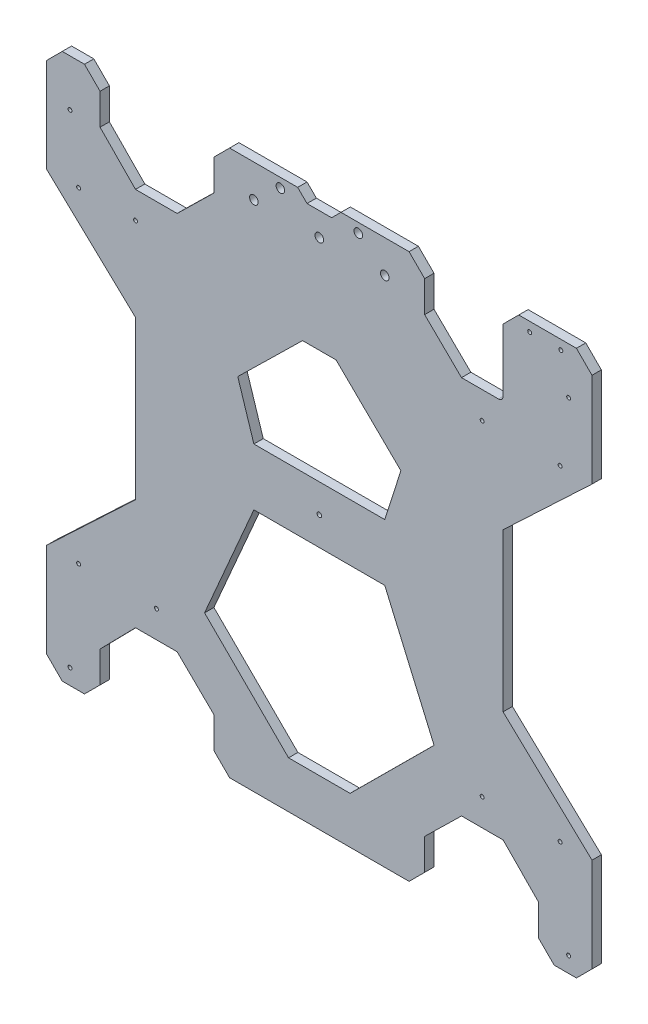
SolidWorks part; units mm, degrees
material "6063-T5"
ref_plane "Piano frontale" through (0, 0, 0) normal (0, 0, 1) x (1, 0, 0)
ref_plane "Piano superiore" through (0, 0, 0) normal (0, 1, 0) x (1, 0, 0)
ref_plane "Piano destro" through (0, 0, 0) normal (1, 0, 0) x (0, 0, -1)
sketch "Schizzo13" plane through (0, 0, 0) normal (0, 0, 1) x (1, 0, 0)
  line L0 (175, 350) -> (175, 0) construction
  line L1 (10, 0) -> (24.282, 0)
  line L2 (0, 279.5) -> (57.0808, 225.6111)
  line L3 (217, 193.2869) -> (227.343, 225.6111)
  line L4 (133, 193.2869) -> (217, 193.2869)
  line L5 (350, 175) -> (0, 175) construction
  line L6 (-60.1887, 10) -> (461.2643, 10) construction
  line L7 (279.5, 279.5) -> (279.5, 175) construction
  line L8 (-12.961, 344) -> (386.8832, 344) construction
  line L9 (-12.961, 329) -> (386.8832, 329) construction
  line L10 (161.1089, 350) -> (167.1089, 344)
  line L11 (279.5, 70.5) -> (175, 70.5) construction
  line L12 (70.5, 70.5) -> (175, 70.5) construction
  line L13 (167.1089, 344) -> (182.8911, 344)
  line L14 (57.0808, 279.5) -> (57.0808, 175) construction
  line L15 (57.0808, 279.5) -> (175, 279.5) construction
  line L16 (175, 279.5) -> (329.5, 279.5) construction
  line L17 (329.5, 70.5) -> (329.5, 279.5) construction
  line L18 (20.5, 70.5) -> (329.5, 70.5) construction
  line L19 (20.5, 70.5) -> (20.5, 279.5) construction
  line L20 (175, 279.5) -> (20.5, 279.5) construction
  line L21 (15, -40.9714) -> (15, 408.5301) construction
  line L22 (335, -40.9714) -> (335, 408.5301) construction
  line L23 (-12.961, 320) -> (386.8832, 320) construction
  line L24 (10, 0) -> (0, 10)
  line L25 (340, 0) -> (350, 10)
  line L26 (107.4046, 340) -> (107.4046, 320)
  line L27 (107.4046, 320) -> (83.7454, 296.8073)
  line L28 (57.0808, 279.5) -> (20.5, 279.5) construction
  line L29 (57.0174, 296.8073) -> (34.282, 320)
  line L30 (83.7454, 296.8073) -> (57.0174, 296.8073)
  line L31 (34.282, 320) -> (34.282, 340)
  line L32 (24.282, 350) -> (10, 350)
  line L33 (133, 193.2869) -> (122.657, 225.6111)
  line L34 (57.0808, 279.5) -> (57.0808, 350) construction
  line L35 (164.2491, 266.3832) -> (185.7509, 266.3832)
  line L36 (122.657, 225.6111) -> (164.2491, 266.3832)
  line L37 (57.0808, 225.6111) -> (57.0808, 175)
  line L38 (227.343, 225.6111) -> (185.7509, 266.3832)
  line L39 (292.9192, 225.6111) -> (292.9192, 124.3889)
  line L40 (350, 279.5) -> (292.9192, 225.6111)
  line L41 (188.8911, 350) -> (182.8911, 344)
  line L42 (117.4046, 350) -> (161.1089, 350)
  line L44 (292.9826, 299.8073) -> (292.9826, 340)
  line L46 (117.4046, 0) -> (232.5954, 0)
  line L47 (266.2546, 296.8073) -> (289.9826, 296.8073)
  line L48 (242.5954, 320) -> (266.2546, 296.8073)
  line L49 (242.5954, 340) -> (242.5954, 320)
  line L50 (350, 70.5) -> (292.9192, 124.3889)
  line L53 (350, 10) -> (350, 70.5)
  line L55 (315.718, 30) -> (315.718, 10)
  line L56 (292.9826, 53.1927) -> (315.718, 30)
  line L57 (266.2546, 53.1927) -> (292.9826, 53.1927)
  line L58 (242.5954, 30) -> (266.2546, 53.1927)
  line L59 (242.5954, 10) -> (242.5954, 30)
  line L60 (107.4046, 10) -> (107.4046, 30)
  line L61 (107.4046, 30) -> (83.7454, 53.1927)
  line L62 (83.7454, 53.1927) -> (57.0174, 53.1927)
  line L63 (57.0174, 53.1927) -> (34.282, 30)
  line L64 (34.282, 30) -> (34.282, 10)
  line L66 (0, 10) -> (0, 70.5)
  line L69 (0, 70.5) -> (57.0808, 124.3889)
  line L70 (57.0808, 124.3889) -> (57.0808, 175)
  line L71 (0, 279.5) -> (0, 340)
  line L72 (188.8911, 350) -> (232.5954, 350)
  line L73 (302.9826, 350) -> (340, 350)
  line L74 (350, 279.5) -> (350, 340)
  line L75 (325.718, 0) -> (340, 0)
  line L76 (24.282, 0) -> (34.282, 10)
  line L77 (117.4046, 0) -> (107.4046, 10)
  line L78 (232.5954, 0) -> (242.5954, 10)
  line L79 (315.718, 10) -> (325.718, 0)
  line L80 (10, 350) -> (0, 340)
  line L81 (24.282, 350) -> (34.282, 340)
  line L82 (107.4046, 340) -> (117.4046, 350)
  line L83 (232.5954, 350) -> (242.5954, 340)
  line L84 (292.9826, 340) -> (302.9826, 350)
  line L85 (340, 350) -> (350, 340)
  line L86 (133, 156.7131) -> (101.3482, 83.6168)
  line L87 (101.3482, 83.6168) -> (155.2542, 30)
  line L88 (155.2542, 30) -> (194.7458, 30)
  line L89 (133, 156.7131) -> (217, 156.7131)
  line L90 (248.6518, 83.6168) -> (194.7458, 30)
  line L91 (217, 156.7131) -> (248.6518, 83.6168)
  circle A0 centre (15, 320) radius 1.25
  circle A1 centre (20.5, 279.5) radius 1.25
  circle A2 centre (57.0808, 279.5) radius 1.25
  circle A3 centre (175, 175) radius 1.5
  arc A4 (289.9826, 296.8073) -> (292.9826, 299.8073) centre (289.9826, 299.8073) ccw
  circle A5 centre (20.5, 70.5) radius 1.25
  circle A6 centre (200, 344) radius 2.75
  circle A7 centre (150, 344) radius 2.75
  circle A8 centre (175, 329) radius 2.75
  circle A9 centre (217, 329) radius 2.75
  circle A10 centre (133, 329) radius 2.75
  circle A11 centre (70.5, 70.5) radius 1.25
  circle A12 centre (279.5, 70.5) radius 1.25
  circle A13 centre (329.5, 70.5) radius 1.25
  circle A14 centre (335, 10) radius 1.25
  circle A15 centre (15, 10) radius 1.25
  circle A16 centre (279.5, 279.5) radius 1.25
  circle A17 centre (329.5, 279.5) radius 1.25
  circle A18 centre (335, 320) radius 1.25
  circle A19 centre (310, 344) radius 1.25
  circle A20 centre (330, 344) radius 1.25
  point P7 (175, 175)
  point P25 (175, 344)
  point P30 (175, 329)
  point P41 (175, 175)
  point P43 (329.5, 175)
  point P46 (15, 320)
  point P54 (335, 320)
  point P55 (335, 10)
  point P56 (15, 10)
  point P57 (15, 320)
  point P58 (335, 320)
  point P59 (15, 10)
  point P60 (335, 10)
  point P93 (292.9826, 296.8073)
  point P108 (175, 344)
  point P155 (175, 156.7131)
  point P156 (175, 30)
  dimension "D5" = 42
  dimension "D6" = 5.5
  dimension "D7" = 25
  dimension "D8" = 15
  dimension "D10" = 154.5
  dimension "D3" = 104.5
  dimension "D17" = 20
  dimension "D2" = 3
  dimension "D9" = 2.5
  dimension "D4" = 104.5
  dimension "D11" = 104.5
  dimension "D15" = 310
  dimension "D16" = 320
extrude "Estrusione-Estrusione2" add sketch "Schizzo13" against normal blind 6
sketch "Schizzo14" plane through (0, 0, 0) normal (0, 0, 1) x (1, 0, 0)
  line L0 (350, 350.0234) -> (0, 350.0234)
  line L2 (0, 350.0234) -> (0, 0)
  line L3 (0, 0) -> (350, 0)
  line L4 (117.4046, 0) -> (232.5954, 0) construction
  line L5 (175, 344) -> (175, 0) construction
  line L6 (350, 350.0234) -> (350, 0)
  line L7 (182.8911, 344) -> (167.1089, 344) construction
  circle A0 centre (175, 223.4858) radius 4.4409
  circle A1 centre (175, 78.9698) radius 4.6362
  dimension "D1" = 350.0234
  dimension "D2" = 350
sketch "Schizzo15" plane through (0, 0, 0) normal (0, 0, 1) x (1, 0, 0)
  text T0 "HackerBot" font "Lobster 1.4" height 14
